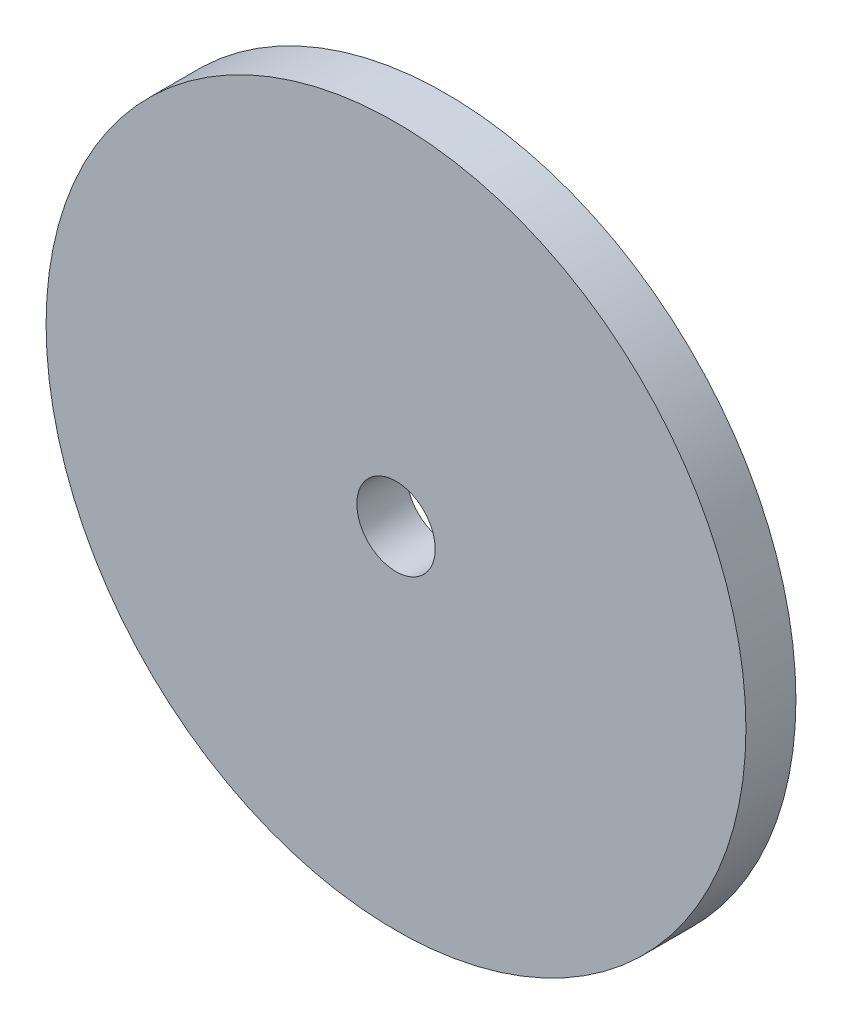
SolidWorks part; units mm, degrees
ref_plane "Front Plane" through (0, 0, 0) normal (0, 0, 1) x (1, 0, 0)
ref_plane "Top Plane" through (0, 0, 0) normal (0, 1, 0) x (1, 0, 0)
ref_plane "Right Plane" through (0, 0, 0) normal (1, 0, 0) x (0, 0, -1)
sketch "Sketch1" plane through (0, 0, 0) normal (0, 0, 1) x (1, 0, 0)
  circle A0 centre (0, 0) radius 22.225
  circle A1 centre (0, 0) radius 2.4892
  dimension "D1" = 44.45
  dimension "D2" = 4.9784
extrude "Boss-Extrude1" add sketch "Sketch1" along normal blind 3.175
